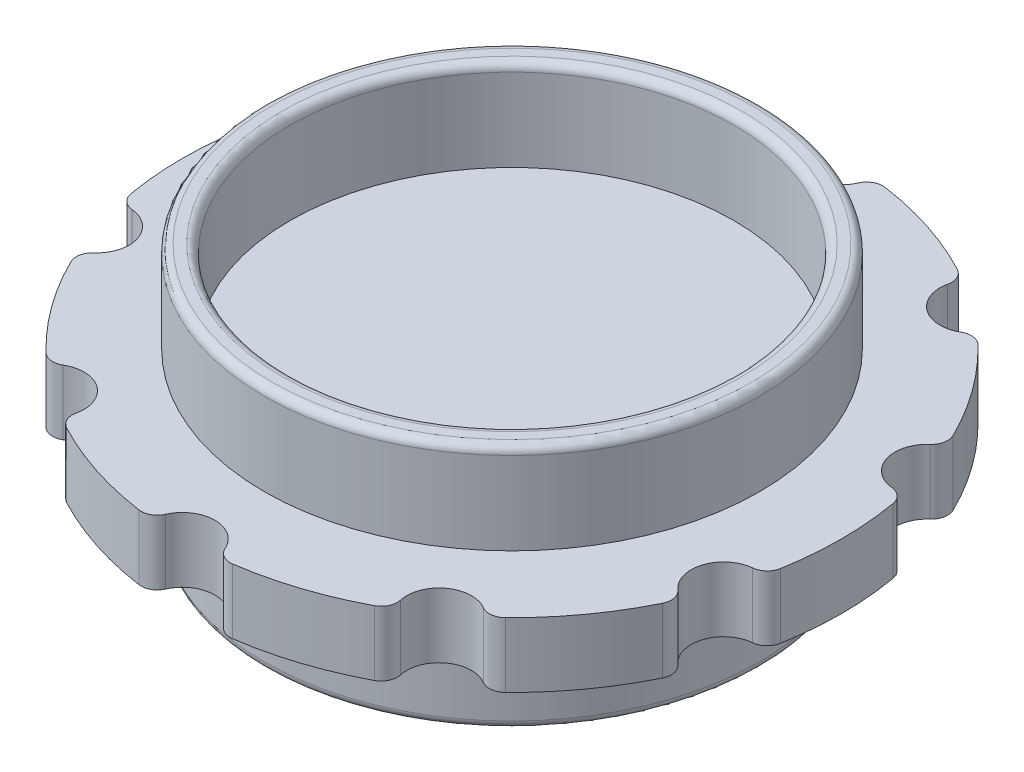
SolidWorks part; units mm, degrees
ref_plane "前视基准面" through (0, 0, 0) normal (0, 0, 1) x (1, 0, 0)
ref_plane "上视基准面" through (0, 0, 0) normal (0, 1, 0) x (1, 0, 0)
ref_plane "右视基准面" through (0, 0, 0) normal (1, 0, 0) x (0, 0, -1)
other "Configuration Table"
sketch "草图1" plane through (0, 0, 0) normal (0, 1, 0) x (1, 0, 0)
  circle A0 centre (0, 0) radius 15.3
  circle A1 centre (0, 0) radius 20.35
  circle A2 centre (0, 0) radius 13.7
  circle A3 centre (0, 20.35) radius 2
  dimension "D1" = 30.6
  dimension "D2" = 40.7
  dimension "D3" = 1.6
  dimension "D4" = 4
extrude "凸台-拉伸1" add sketch "草图1" along normal mid plane 15.2 contours A0 | A2
extrude "凸台-拉伸2" add sketch "草图1<3>" along normal mid plane 4 contours A1
sketch "草图1<3>" plane through (0, 0, 0) normal (0, 1, 0) x (1, 0, 0) same geometry as "草图1"
extrude "切除-拉伸1" cut sketch "草图1<4>" against normal through all both and the other way through all contours A3
sketch "草图1<4>" plane through (0, 0, 0) normal (0, 1, 0) x (1, 0, 0) same geometry as "草图1"
fillet "圆角1" radius 1 2 edges at (1.9976, 0, -20.2517) (-1.9976, 0, -20.2517)
pattern_circular "阵列(圆周)1" count 10 over 360 about axis through (0, 2, 0) along (0, -1, 0) of "切除-拉伸1", "圆角1"
fillet "圆角2" radius 0.5 4 edges at (0, -7.6, 13.7) (0, -7.6, 15.3) (0, 7.6, 13.7) (0, 7.6, 15.3)
sketch "草图2" plane through (0, 2, 0) normal (0, 1, 0) x (1, 0, 0)
  line L0 (0, 20.35) -> (11.9614, 16.4635)
  line L1 (-11.9614, 16.4635) -> (0, 20.35)
  arc A0 (-1.834, 19.5523) -> (1.834, 19.5523) centre (0, 20.35) ccw construction
  arc A1 (10.0088, 16.8962) -> (12.9763, 14.7401) centre (11.9614, 16.4635) ccw construction
  arc A2 (-12.9763, 14.7401) -> (-10.0088, 16.8962) centre (-11.9614, 16.4635) ccw construction
  point P6 (0, 0)
  point P13 (0, 0)
  dimension "D1" = 12.577
  dimension "D2" = 12.577
